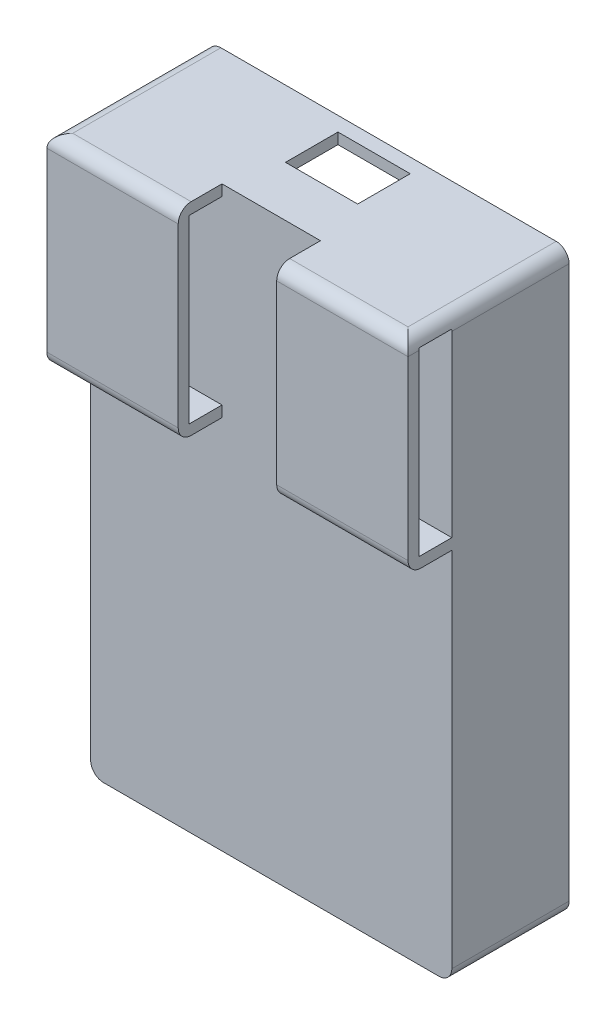
SolidWorks part; units mm, degrees
ref_plane "Front Plane" through (0, 0, 0) normal (0, 0, 1) x (1, 0, 0)
ref_plane "Top Plane" through (0, 0, 0) normal (0, 1, 0) x (1, 0, 0)
ref_plane "Right Plane" through (0, 0, 0) normal (1, 0, 0) x (0, 0, -1)
sketch "Sketch1" plane through (0, 0, 0) normal (0, 1, 0) x (1, 0, 0)
  line L1 (0, 0) -> (83.82, 0)
  line L2 (0, 0) -> (0, 27.225)
  line L3 (0, 27.225) -> (83.82, 27.225)
  line L4 (83.82, 0) -> (83.82, 27.225)
  dimension "D1" = 83.82
  dimension "D2" = 27.225
extrude "Boss-Extrude1" add sketch "Sketch1" along normal blind 87.122
shell "Shell1" thickness 2.54 removed face at (41.91, 43.561, -27.225)
sketch "Sketch12" plane through (0, 87.122, 0) normal (0, 1, 0) x (1, 0, 0)
  line L1 (0, 0) -> (83.82, 0)
  line L2 (0, 0) -> (0, 27.225)
  line L3 (0, 27.225) -> (83.82, 27.225)
  line L4 (83.82, 0) -> (83.82, 27.225)
extrude "Boss-Extrude6" add sketch "Sketch12" along normal blind 46.99
shell "Shell2" thickness 2.54 removed face at (41.91, 67.056, -27.225)
sketch "Sketch5" plane through (0, 88.392, -2.54) normal (0, 0, -1) x (1, 0, 0)
  line L0 (2.54, 1.27) -> (81.28, 1.27) construction
  line L3 (2.54, -43.18) -> (2.54, 1.27) construction
  circle A0 centre (15.24, -29.845) radius 3.175
  circle A1 centre (15.24, -29.845) radius 1.5
  circle A2 centre (15.24, -9.525) radius 3.175
  circle A3 centre (15.24, -9.525) radius 1.5
  circle A4 centre (49.53, -9.525) radius 3.175
  circle A5 centre (49.53, -9.525) radius 1.5
  circle A6 centre (49.53, -29.845) radius 3.175
  circle A7 centre (49.53, -29.845) radius 1.5
  dimension "D4" = 6.35
  dimension "D5" = 6.35
  dimension "D6" = 6.35
  dimension "D7" = 6.35
  dimension "D8" = 3
  dimension "D9" = 3
  dimension "D10" = 3
  dimension "D11" = 3
  dimension "D1" = 20.32
  dimension "D2" = 10.795
  dimension "D3" = 34.29
  dimension "D12" = 12.7
extrude "Boss-Extrude7" add sketch "Sketch5" along normal blind 1.905
sketch "Sketch14" plane through (0, 134.112, 0) normal (0, 1, 0) x (1, 0, 0)
  line L0 (0, 27.225) -> (0, 0) construction
  line L1 (50.292, 23.876) -> (33.528, 23.876)
  line L2 (50.292, 23.876) -> (50.292, 11.684)
  line L3 (50.292, 11.684) -> (33.528, 11.684)
  line L4 (33.528, 23.876) -> (33.528, 11.684)
  line L5 (50.292, 23.876) -> (33.528, 11.684) construction
  line L6 (50.292, 11.684) -> (33.528, 23.876) construction
  line L7 (0, 0) -> (83.82, 0) construction
  point P0 (41.91, 17.78)
  dimension "D1" = 16.764
  dimension "D2" = 12.192
  dimension "D3" = 41.91
  dimension "D4" = 17.78
extrude "Cut-Extrude10" cut sketch "Sketch14" against normal up to next
sketch "Sketch15" plane through (0, 0, 0) normal (0, 0, 1) x (1, 0, 0)
  line L1 (0, 134.112) -> (30.48, 134.112)
  line L2 (0, 134.112) -> (0, 87.122)
  line L3 (0, 87.122) -> (30.48, 87.122)
  line L4 (30.48, 134.112) -> (30.48, 87.122)
  line L5 (83.82, 134.112) -> (53.34, 134.112)
  line L6 (83.82, 134.112) -> (83.82, 87.122)
  line L7 (83.82, 87.122) -> (53.34, 87.122)
  line L8 (53.34, 134.112) -> (53.34, 87.122)
  dimension "D1" = 30.48
  dimension "D2" = 30.48
  dimension "D3" = 46.99
  dimension "D4" = 46.99
extrude "Boss-Extrude8" add sketch "Sketch15" along normal blind 10.16
sketch "Sketch16" plane through (0, 0, 0) normal (-1, 0, 0) x (0, 0, 1)
  line L0 (10.16, 134.112) -> (10.16, 87.122) construction
  line L1 (7.62, 89.662) -> (0, 89.662)
  line L2 (7.62, 89.662) -> (7.62, 131.572)
  line L3 (7.62, 131.572) -> (0, 131.572)
  line L4 (0, 89.662) -> (0, 131.572)
  line L5 (10.16, 87.122) -> (0, 87.122) construction
  line L6 (-27.225, 134.112) -> (10.16, 134.112) construction
  line L8 (0, 87.122) -> (0, 0) construction
  dimension "D1" = 2.54
  dimension "D2" = 2.54
  dimension "D3" = 2.54
extrude "Cut-Extrude11" cut sketch "Sketch16" against normal through all
chamfer "Chamfer1" distance 5.08 angle 45 4 edges at (81.28, 2.54, -14.8825) (2.54, 2.54, -14.8825) (2.54, 84.582, -14.8825) (81.28, 84.582, -14.8825)
sketch "Sketch17" plane through (0, 0, -27.225) normal (0, 0, -1) x (-1, 0, 0)
  line L0 (-83.82, 134.112) -> (-83.82, 0) construction
  line L1 (-81.28, 87.122) -> (-2.54, 87.122) construction
  line L2 (0, 134.112) -> (0, 0) construction
  line L3 (-83.82, 0) -> (0, 0) construction
  circle A0 centre (-3, 84.122) radius 1.5
  circle A1 centre (-80.82, 84.122) radius 1.5
  circle A2 centre (-80.82, 3) radius 1.5
  circle A3 centre (-3, 3) radius 1.5
  dimension "D1" = 3
  dimension "D2" = 3
  dimension "D3" = 3
  dimension "D7" = 3
  dimension "D4" = 3
  dimension "D5" = 3
  dimension "D6" = 3
  dimension "D8" = 3
extrude "Cut-Extrude12" cut sketch "Sketch17" against normal blind 10
fillet "Fillet1" radius 3 8 edges at (68.58, 134.112, 10.16) (15.24, 134.112, 10.16) (68.58, 87.122, 10.16) (15.24, 87.122, 10.16) (83.82, 134.112, -8.5325) (83.82, 0, -13.6125) (0, 0, -13.6125) (0, 134.112, -8.5325)
